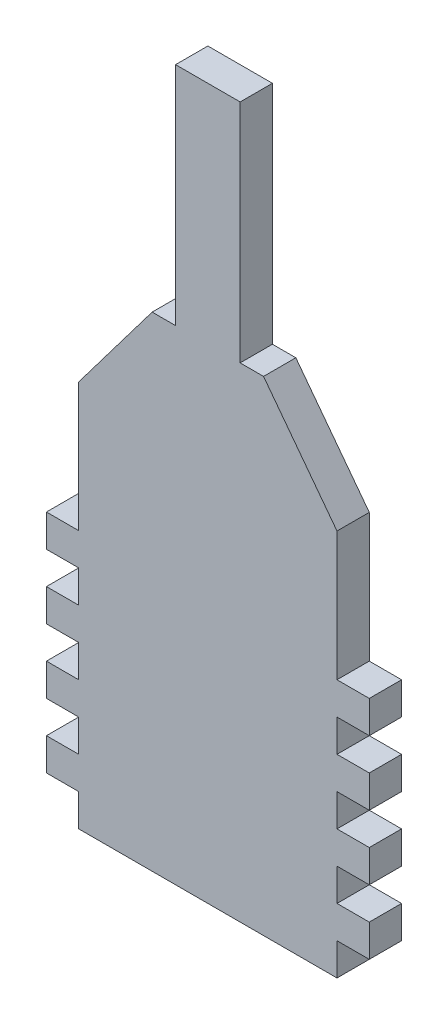
SolidWorks part; units mm, degrees
ref_plane "Plan de face" through (0, 0, 0) normal (0, 0, 1) x (1, 0, 0)
ref_plane "Plan de dessus" through (0, 0, 0) normal (0, 1, 0) x (1, 0, 0)
ref_plane "Plan de droite" through (0, 0, 0) normal (1, 0, 0) x (0, 0, -1)
sketch "Esquisse1" plane through (0, 0, 0) normal (0, 0, 1) x (1, 0, 0)
  line L29 (-88.4214, 20.835) -> (-88.4214, 25.835)
  line L30 (-93.4214, 25.835) -> (-88.4214, 25.835)
  line L31 (-93.4214, 25.835) -> (-93.4214, 30.835)
  line L32 (-93.4214, 30.835) -> (-88.4214, 30.835)
  line L33 (-88.4214, 30.835) -> (-88.4214, 35.835)
  line L34 (-93.4214, 35.835) -> (-88.4214, 35.835)
  line L35 (-93.4214, 35.835) -> (-93.4214, 40.835)
  line L36 (-93.4214, 40.835) -> (-88.4214, 40.835)
  line L37 (-88.4214, 40.835) -> (-88.4214, 45.835)
  line L38 (-93.4214, 45.835) -> (-88.4214, 45.835)
  line L39 (-93.4214, 45.835) -> (-93.4214, 50.835)
  line L40 (-93.4214, 50.835) -> (-88.4214, 50.835)
  line L43 (-73.4214, 95.835) -> (-73.4214, 130.835)
  line L48 (-73.4214, 130.835) -> (-63.4214, 130.835)
  line L49 (-88.4214, 20.835) -> (-48.4214, 20.835)
  line L52 (-63.4214, 95.835) -> (-63.4214, 130.835)
  line L53 (-43.4214, 50.835) -> (-48.4214, 50.835)
  line L54 (-43.4214, 45.835) -> (-43.4214, 50.835)
  line L55 (-43.4214, 45.835) -> (-48.4214, 45.835)
  line L56 (-48.4214, 40.835) -> (-48.4214, 45.835)
  line L57 (-43.4214, 40.835) -> (-48.4214, 40.835)
  line L58 (-43.4214, 35.835) -> (-43.4214, 40.835)
  line L59 (-43.4214, 35.835) -> (-48.4214, 35.835)
  line L60 (-48.4214, 30.835) -> (-48.4214, 35.835)
  line L61 (-43.4214, 30.835) -> (-48.4214, 30.835)
  line L62 (-43.4214, 25.835) -> (-43.4214, 30.835)
  line L63 (-43.4214, 25.835) -> (-48.4214, 25.835)
  line L64 (-48.4214, 20.835) -> (-48.4214, 25.835)
  line L65 (-88.4214, 55.835) -> (-93.4214, 55.835)
  line L66 (-93.4214, 55.835) -> (-93.4214, 60.835)
  line L67 (-93.4214, 60.835) -> (-88.4214, 60.835)
  line L68 (-88.4214, 50.835) -> (-88.4214, 55.835)
  line L70 (-68.4214, 130.835) -> (-68.4214, 20.835) construction
  line L71 (-43.4214, 60.835) -> (-48.4214, 60.835)
  line L72 (-43.4214, 55.835) -> (-43.4214, 60.835)
  line L73 (-48.4214, 55.835) -> (-43.4214, 55.835)
  line L74 (-48.4214, 50.835) -> (-48.4214, 55.835)
  line L76 (-77.0464, 95.835) -> (-88.4214, 80.7852)
  line L77 (-88.4214, 60.835) -> (-88.4214, 80.7852)
  line L78 (-77.0464, 95.835) -> (-73.4214, 95.835)
  line L79 (-59.7964, 95.835) -> (-63.4214, 95.835)
  line L80 (-48.4214, 60.835) -> (-48.4214, 80.7852)
  line L81 (-59.7964, 95.835) -> (-48.4214, 80.7852)
  line L82 (-63.4214, 95.835) -> (-63.4214, 130.835)
  point P5 (0, 0)
  dimension "D1" = 5
  dimension "D2" = 75
  dimension "D3" = 5
  dimension "D4" = 5
  dimension "D6" = 5
  dimension "D7" = 5
  dimension "D8" = 35
extrude "Boss.-Extru.1" add sketch "Esquisse1" along normal blind 5 contours L53 L54 L55 L29 L31 L32 L33 L34 L35 L36 | L40 L43 | L48 L43 L78 L76 L77 L67 L66 L65 L68 L40 L39 L38 L37 L36 L35 L34 L33 L32 L31 L30 L29 L49 L64 L63 L62 L61 L60 L59 L58 L57 L56 L55 L54 L53 L74 L73 L72 L71 L80 L81 L79 L52 region at (-68.4214, 61.4985, 0)
